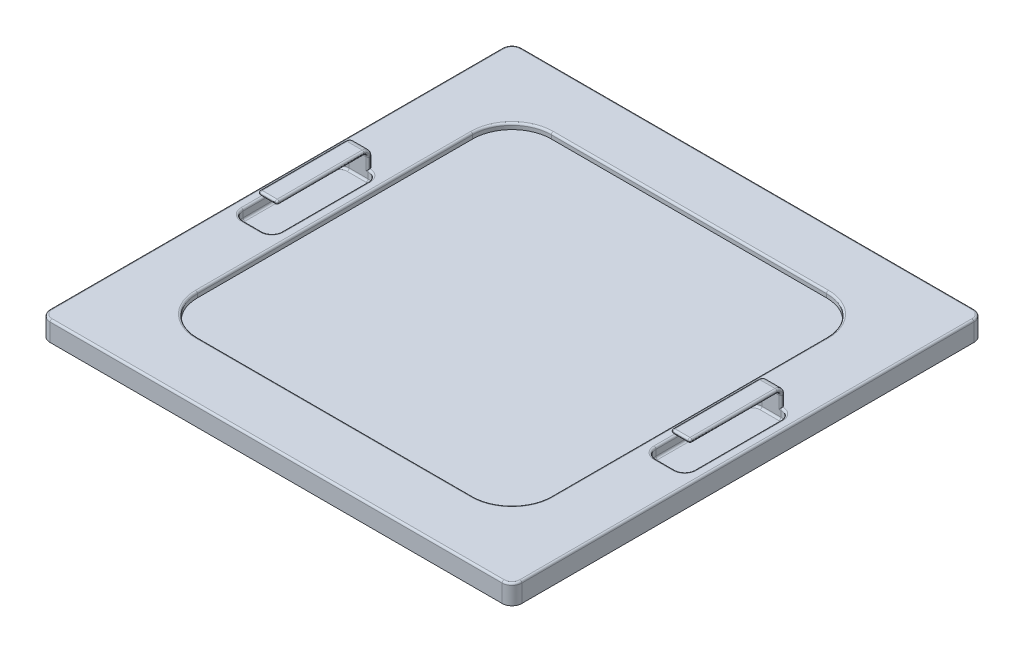
SolidWorks part; units mm, degrees
ref_plane "前视基准面" through (0, 0, 0) normal (0, 0, 1) x (1, 0, 0)
ref_plane "上视基准面" through (0, 0, 0) normal (0, 1, 0) x (1, 0, 0)
ref_plane "右视基准面" through (0, 0, 0) normal (1, 0, 0) x (0, 0, -1)
other "Configuration Table"
sketch "草图1" plane through (0, 0, 0) normal (0, 1, 0) x (1, 0, 0)
  line L1 (-115, -120) -> (115, -120)
  line L2 (-120, -115) -> (-120, 115)
  line L3 (-115, 120) -> (115, 120)
  line L4 (120, -115) -> (120, 115)
  line L5 (-120, -120) -> (120, 120) construction
  line L6 (-120, 120) -> (120, -120) construction
  arc A0 (-115, -120) -> (-120, -115) centre (-115, -115) cw
  arc A1 (115, -120) -> (120, -115) centre (115, -115) ccw
  arc A2 (115, 120) -> (120, 115) centre (115, 115) cw
  arc A3 (-120, 115) -> (-115, 120) centre (-115, 115) cw
  point P0 (0, 0)
  dimension "D3" = 5
  dimension "D1" = 240
  dimension "D2" = 240
extrude "凸台-拉伸1" add sketch "草图1" along normal blind 10
sketch "草图2" plane through (0, 10, 0) normal (0, 1, 0) x (1, 0, 0)
  line L1 (-70, -90) -> (70, -90)
  line L2 (-90, -70) -> (-90, 70)
  line L3 (-70, 90) -> (70, 90)
  line L4 (90, -70) -> (90, 70)
  line L5 (-90, -90) -> (90, 90) construction
  line L6 (-90, 90) -> (90, -90) construction
  arc A0 (-90, -70) -> (-70, -90) centre (-70, -70) ccw
  arc A1 (70, -90) -> (90, -70) centre (70, -70) ccw
  arc A2 (70, 90) -> (90, 70) centre (70, 70) cw
  arc A3 (-90, 70) -> (-70, 90) centre (-70, 70) cw
  point P0 (0, 0)
  dimension "D3" = 20
  dimension "D1" = 180
  dimension "D2" = 180
extrude "切除-拉伸1" cut sketch "草图2" against normal blind 10
sketch "草图3" plane through (0, 0, -120) normal (0, 0, -1) x (-1, 0, 0)
  line L0 (115, 10) -> (115, 0) construction
  line L1 (-110, 4.057) -> (115, 4.057)
  line L2 (-110, 4.057) -> (-110, 7.1431)
  line L3 (-110, 7.1431) -> (115, 7.1431)
  line L4 (115, 4.057) -> (115, 7.1431)
  line L5 (-110, 4.057) -> (115, 7.1431) construction
  line L6 (-110, 7.1431) -> (115, 4.057) construction
  point P0 (2.5, 5.6001)
extrude "凸台-拉伸2" add sketch "草图3" against normal blind 221 separate body
sketch "草图5" plane through (0, 10, 0) normal (0, 1, 0) x (1, 0, 0)
  line L0 (-120, 0) -> (-90, 0)
  line L1 (-120, 115) -> (-120, -115) construction
  line L2 (-90, 70) -> (-90, -70) construction
  line L3 (100.1833, -26.9575) -> (109.8167, -26.9575)
  line L4 (90, -70) -> (90, 70) construction
  line L5 (90, 0) -> (120, 0)
  line L6 (120, -115) -> (120, 115) construction
  line L7 (-109.8167, -26.9575) -> (-100.1833, -26.9575)
  line L8 (-114.8167, -21.9575) -> (-114.8167, 21.9575)
  line L9 (-109.8167, 26.9575) -> (-100.1833, 26.9575)
  line L10 (-95.1833, -21.9575) -> (-95.1833, 21.9575)
  line L11 (-114.8167, -26.9575) -> (-95.1833, 26.9575) construction
  line L12 (-114.8167, 26.9575) -> (-95.1833, -26.9575) construction
  line L13 (100.1833, 26.9575) -> (109.8167, 26.9575)
  line L14 (95.1833, -21.9575) -> (95.1833, 21.9575)
  line L15 (114.8167, -21.9575) -> (114.8167, 21.9575)
  arc A0 (-114.8167, 21.9575) -> (-109.8167, 26.9575) centre (-109.8167, 21.9575) cw
  arc A1 (-109.8167, -26.9575) -> (-114.8167, -21.9575) centre (-109.8167, -21.9575) cw
  arc A2 (-100.1833, -26.9575) -> (-95.1833, -21.9575) centre (-100.1833, -21.9575) ccw
  arc A3 (-100.1833, 26.9575) -> (-95.1833, 21.9575) centre (-100.1833, 21.9575) cw
  arc A4 (100.1833, -26.9575) -> (95.1833, -21.9575) centre (100.1833, -21.9575) cw
  arc A5 (109.8167, 26.9575) -> (114.8167, 21.9575) centre (109.8167, 21.9575) cw
  arc A6 (95.1833, 21.9575) -> (100.1833, 26.9575) centre (100.1833, 21.9575) cw
  arc A7 (109.8167, -26.9575) -> (114.8167, -21.9575) centre (109.8167, -21.9575) ccw
  point P6 (-105, 0)
  dimension "D1" = 5
extrude "切除-拉伸2" cut sketch "草图5" against normal blind 5 contours A3 L9 A0 L8 L0 L10 | L7 A2 L10 L0 L8 A1 | A6 L14 L5 L15 A5 L13 | L3 A7 L15 L5 L14 A4
sketch "草图6" plane through (0, 0, -26.9575) normal (0, 0, 1) x (1, 0, 0)
  line L1 (-109.8167, 7.1431) -> (-100.1833, 7.1431)
  line L2 (-109.8167, 7.1431) -> (-109.8167, 13.722)
  line L3 (-109.8167, 13.722) -> (-100.1833, 13.722)
  line L4 (-100.1833, 7.1431) -> (-100.1833, 13.722)
  dimension "D1" = 9.6333
extrude "凸台-拉伸3" add sketch "草图6" against normal blind 2
sketch "草图9" plane through (-109.8167, 0, 0) normal (-1, 0, 0) x (0, 0, 1)
  line L0 (-26.9575, 13.722) -> (-26.9575, 10) construction
  line L1 (-24.9575, 17.2001) -> (19.2635, 17.2001)
  line L3 (-24.9575, 19.2001) -> (19.2635, 19.2001)
  line L4 (19.2635, 17.2001) -> (19.2635, 19.2001)
  line L6 (-28.9575, 15.2001) -> (-28.9575, 13.3043)
  line L7 (-28.9575, 13.3043) -> (-26.9575, 13.3043)
  line L8 (-26.9575, 15.2001) -> (-26.9575, 13.3043)
  arc A0 (-26.9575, 15.2001) -> (-24.9575, 17.2001) centre (-24.9575, 15.2001) cw
  arc A1 (-24.9575, 19.2001) -> (-28.9575, 15.2001) centre (-24.9575, 15.2001) ccw
  dimension "D1" = 2
  dimension "D2" = 4
extrude "凸台-拉伸4" add sketch "草图9" against normal blind 9.6333
fillet "圆角1" radius 1 14 edges at (-100.1833, 12.6001, -26.9575) (-109.8167, 16.6143, -26.3717) (-100.1833, 16.6143, -26.3717) (-109.8167, 12.6001, -26.9575) (-100.1833, 12.6001, -28.9575) (-109.8167, 18.0285, -27.7859) (-100.1833, 18.0285, -27.7859) (-109.8167, 12.6001, -28.9575) (-105, 17.2001, 19.2635) (-109.8167, 17.2001, -2.847) (-100.1833, 17.2001, -2.847) (-109.8167, 19.2001, -2.847) (-100.1833, 19.2001, -2.847) (-105, 19.2001, 19.2635)
fillet "圆角3" radius 1 8 edges at (-113.3522, 5, -25.4931) (-105, 5, -26.9575) (-96.6478, 5, -25.4931) (-95.1833, 5, 0) (-96.6478, 5, 25.4931) (-105, 5, 26.9575) (-113.3522, 5, 25.4931) (-114.8167, 5, 0)
fillet "圆角4" radius 1 9 edges at (-100.6833, 10, -26.9575) (-109.3167, 10, -26.9575) (-113.3522, 10, -25.4931) (-114.8167, 10, 0) (-113.3522, 10, 25.4931) (-105, 10, 26.9575) (-96.6478, 10, 25.4931) (-95.1833, 10, 0) (-96.6478, 10, -25.4931)
sketch "草图10" plane through (0, 10, 0) normal (0, 1, 0) x (1, 0, 0)
  line L0 (-115, -120) -> (115, -120) construction
  line L1 (0, -120) -> (142.4422, -120)
  line L2 (0, -120) -> (0, 132.347)
  line L3 (0, 132.347) -> (142.4422, 132.347)
  line L4 (142.4422, -120) -> (142.4422, 132.347)
extrude "切除-拉伸3" cut sketch "草图10" against normal blind 36.7
mirror "镜向1" about plane through (0, -26.7, 120) normal (-1, 0, 0) of bodies 113
fillet "圆角5" radius 1 8 edges at (118.5355, 10, -118.5355) (120, 10, 0) (118.5355, 10, 118.5355) (0, 10, 120) (-118.5355, 10, 118.5355) (-120, 10, 0) (-118.5355, 10, -118.5355) (0, 10, -120)
fillet "圆角6" radius 1 16 edges at (-84.1421, 0, 84.1421) (-90, 0, 0) (-84.1421, 0, -84.1421) (0, 0, 90) (0, 0, -90) (-84.1421, 10, 84.1421) (0, 10, -90) (0, 10, 90) (-84.1421, 10, -84.1421) (-90, 10, 0) (84.1421, 10, -84.1421) (90, 10, 0) (84.1421, 10, 84.1421) (84.1421, 0, 84.1421) (90, 0, 0) (84.1421, 0, -84.1421)
